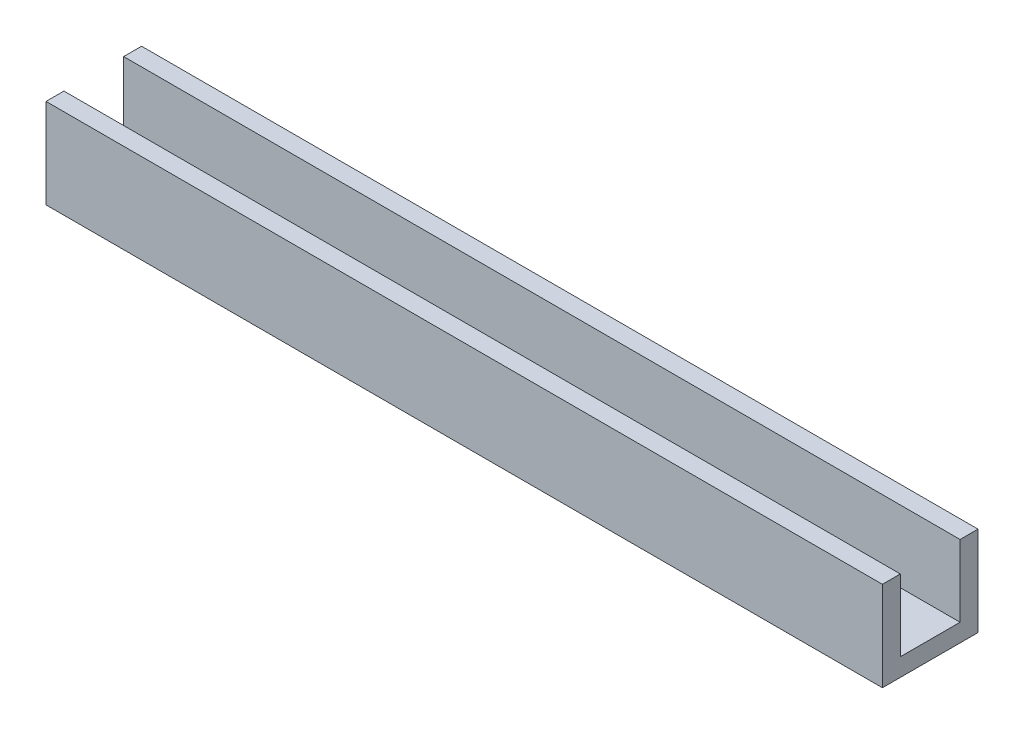
SolidWorks part; units mm, degrees
ref_plane "Front Plane" through (0, 0, 0) normal (0, 0, 1) x (1, 0, 0)
ref_plane "Top Plane" through (0, 0, 0) normal (0, 1, 0) x (1, 0, 0)
ref_plane "Right Plane" through (0, 0, 0) normal (1, 0, 0) x (0, 0, -1)
sketch "Sketch3" plane through (0, 0, 0) normal (0, 1, 0) x (1, 0, 0)
  line L1 (70, -8) -> (-70, -8)
  line L2 (70, -8) -> (70, 8)
  line L3 (70, 8) -> (-70, 8)
  line L4 (-70, -8) -> (-70, 8)
  line L5 (70, -8) -> (-70, 8) construction
  line L6 (70, 8) -> (-70, -8) construction
  line L7 (70, -5) -> (-70, -5)
  line L8 (70, -5) -> (70, 5)
  line L9 (70, 5) -> (-70, 5)
  line L10 (-70, -5) -> (-70, 5)
  line L11 (70, -5) -> (-70, 5) construction
  line L12 (70, 5) -> (-70, -5) construction
  point P0 (0, 0)
  point P6 (0, 0)
  dimension "D1" = 16
  dimension "D2" = 3
  dimension "D3" = 140
extrude "Boss-Extrude2" add sketch "Sketch3" along normal blind 3 contours L2 L9 L4 L7 region at (0, 0, 0)
extrude "Boss-Extrude3" add sketch "Sketch3<3>" along normal blind 15 contours L2 L7 L4 L1 | L9 L2 L3 L4 region at (0, 0, 6.5) region at (0, 0, -6.5)
sketch "Sketch3<3>" plane through (0, 0, 0) normal (0, 1, 0) x (1, 0, 0) same geometry as "Sketch3"
